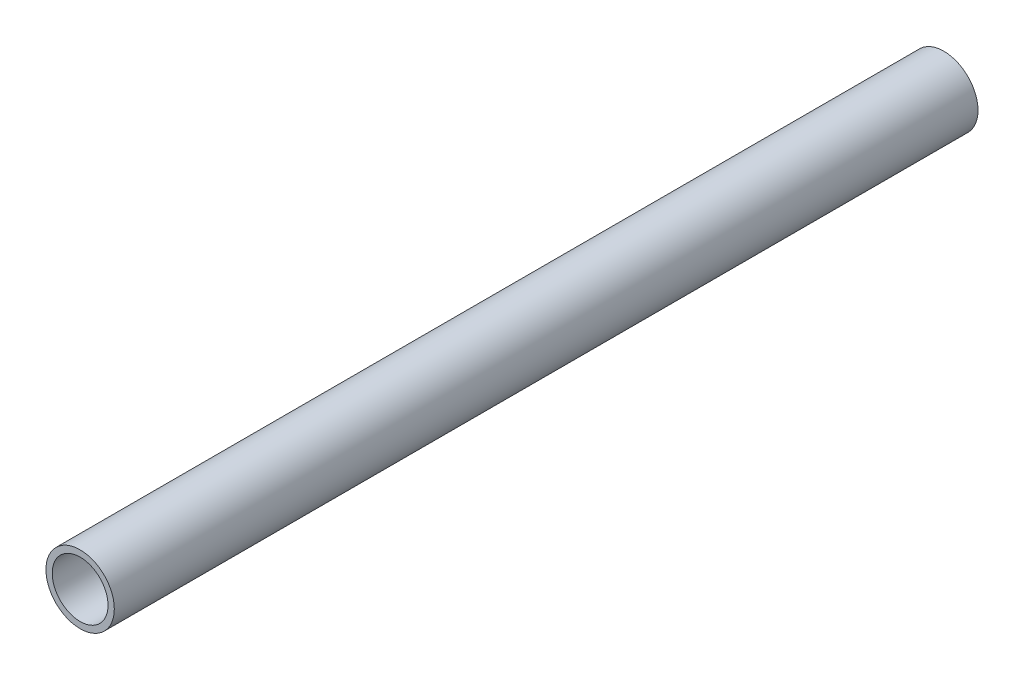
SolidWorks part; units mm, degrees
ref_plane "Front Plane" through (0, 0, 0) normal (0, 0, 1) x (1, 0, 0)
ref_plane "Top Plane" through (0, 0, 0) normal (0, 1, 0) x (1, 0, 0)
ref_plane "Right Plane" through (0, 0, 0) normal (1, 0, 0) x (0, 0, -1)
sketch "Sketch1" plane through (0, 0, 0) normal (0, 0, 1) x (1, 0, 0)
  circle A0 centre (0, 0) radius 30.1625
  dimension "Pipe OD" = 60.325
extrude "Extrude-Thin1" add sketch "Sketch1" along normal blind 762 thin thin type one direction reverse wall 5.5372
